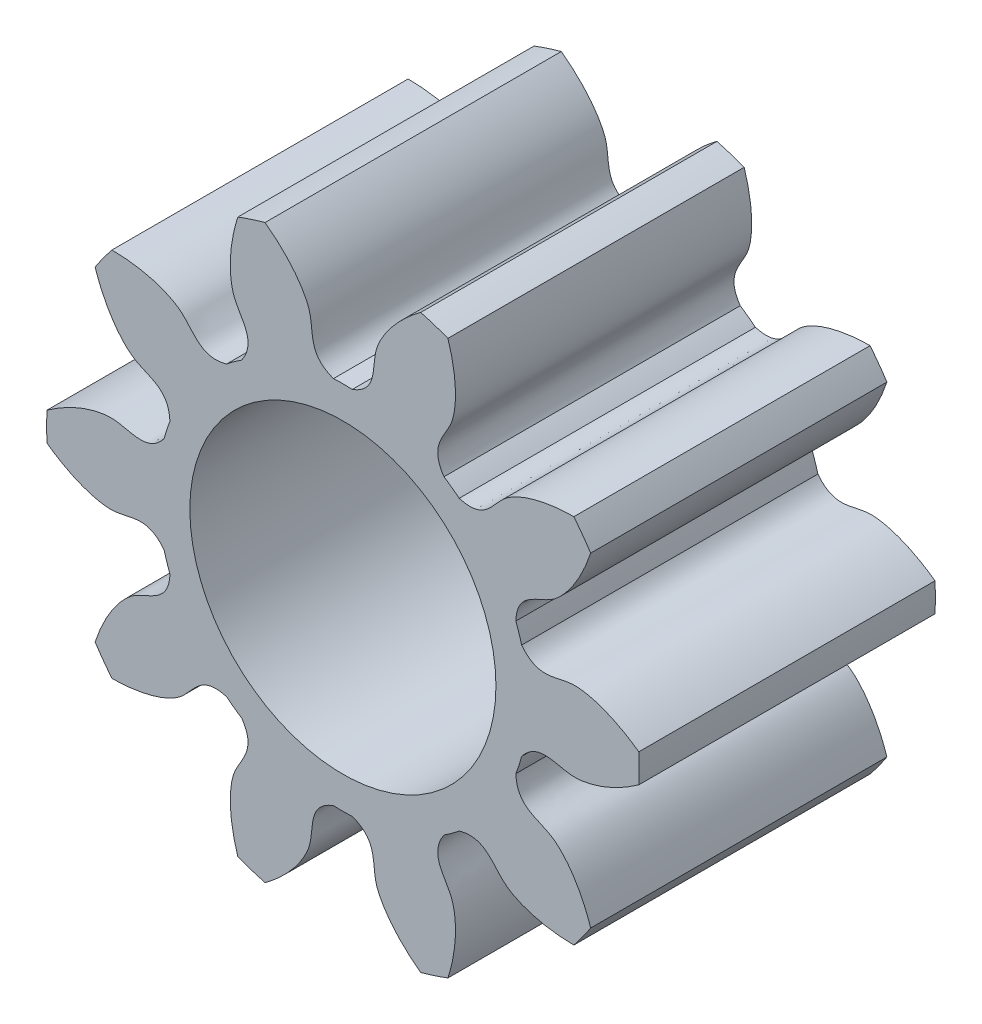
SolidWorks part; units mm, degrees
ref_plane "前视基准面" through (0, 0, 0) normal (0, 0, 1) x (1, 0, 0)
ref_plane "上视基准面" through (0, 0, 0) normal (0, 1, 0) x (1, 0, 0)
ref_plane "右视基准面" through (0, 0, 0) normal (1, 0, 0) x (0, 0, -1)
sketch "草图1" plane through (0, 0, 0) normal (0, 0, 1) x (1, 0, 0)
  circle A0 centre (0, 0) radius 3
extrude "凸台-拉伸1" add sketch "草图1" along normal blind 3
ref_axis "基准轴1" through (0, 0, -0.3) along (0, 0, 1)
sketch "草图2" plane through (0, 0, 0) normal (0, 0, 1) x (1, 0, 0)
  line L0 (0, 0) -> (0, 3) construction
  circle A0 centre (0, 0) radius 3 construction
  arc A1 (0.0952, 1.8726) -> (-0.0952, 1.8726) centre (0, 0) ccw
  arc A2 (2.1268, 3.3471) -> (-2.1268, 3.3471) centre (0, 0) ccw
  spline S0 degree 3 poles (0.0952, 1.8726) (0.3627, 1.9703) (0.2869, 2.1853) (0.3443, 2.3623) (0.3473, 2.3708) (0.3507, 2.38) (0.3546, 2.3901) (0.3591, 2.4009) (0.3642, 2.4126) (0.3699, 2.4249) (0.3763, 2.438) (0.3834, 2.4518) (0.3911, 2.4663) (0.3997, 2.4815) (0.409, 2.4972) (0.4191, 2.5136) (0.4301, 2.5306) (0.4419, 2.5481) (0.4546, 2.5662) (0.4682, 2.5848) (0.4828, 2.6038) (0.4983, 2.6233) (0.5148, 2.6432) (0.5323, 2.6634) (0.5509, 2.684) (0.5705, 2.7049) (0.5911, 2.7261) (0.6129, 2.7476) (0.6358, 2.7692) (0.6598, 2.791) (0.6849, 2.8129) (0.7112, 2.835) (0.7386, 2.8571) (0.7672, 2.8792) (0.7971, 2.9013) (0.8281, 2.9234) (0.8603, 2.9453) (0.8938, 2.9671) (0.9285, 2.9888) (0.9644, 3.0102) (1.0015, 3.0314) (1.0399, 3.0522) (1.0796, 3.0728) (1.1204, 3.0929) (1.1626, 3.1126) (1.2059, 3.1319) (1.2506, 3.1506) (1.2964, 3.1688) (1.3435, 3.1864) (1.3918, 3.2034) (1.4414, 3.2197) (1.4921, 3.2353) (1.5441, 3.2501) (1.5972, 3.2642) (1.6516, 3.2773) (1.7071, 3.2896) (1.7638, 3.301) (1.8216, 3.3114) (1.8805, 3.3208) (1.9405, 3.3291) (2.0227, 3.3388) (2.0849, 3.3443) (2.1268, 3.3471) knots 0 0 0 0 0.201721 0.204697 0.208023 0.211699 0.215726 0.220102 0.224829 0.229906 0.235332 0.241109 0.247237 0.253714 0.260541 0.267719 0.275246 0.283124 0.291352 0.29993 0.308858 0.318136 0.327765 0.337743 0.348072 0.358751 0.36978 0.381158 0.392888 0.404967 0.417396 0.430176 0.443305 0.456785 0.470615 0.484795 0.499325 0.514205 0.529435 0.545016 0.560946 0.577227 0.593858 0.610839 0.62817 0.645851 0.663882 0.682264 0.700995 0.720077 0.739509 0.759291 0.779423 0.799905 0.820737 0.84192 0.863452 0.885335 0.907568 0.930151 0.953084 1 1 1 1
  spline S1 degree 3 poles (-0.0952, 1.8726) (-0.3627, 1.9703) (-0.2869, 2.1853) (-0.3443, 2.3623) (-0.3473, 2.3708) (-0.3507, 2.38) (-0.3546, 2.3901) (-0.3591, 2.4009) (-0.3642, 2.4126) (-0.3699, 2.4249) (-0.3763, 2.438) (-0.3834, 2.4518) (-0.3911, 2.4663) (-0.3997, 2.4815) (-0.409, 2.4972) (-0.4191, 2.5136) (-0.4301, 2.5306) (-0.4419, 2.5481) (-0.4546, 2.5662) (-0.4682, 2.5848) (-0.4828, 2.6038) (-0.4983, 2.6233) (-0.5148, 2.6432) (-0.5323, 2.6634) (-0.5509, 2.684) (-0.5705, 2.7049) (-0.5911, 2.7261) (-0.6129, 2.7476) (-0.6358, 2.7692) (-0.6598, 2.791) (-0.6849, 2.8129) (-0.7112, 2.835) (-0.7386, 2.8571) (-0.7672, 2.8792) (-0.7971, 2.9013) (-0.8281, 2.9234) (-0.8603, 2.9453) (-0.8938, 2.9671) (-0.9285, 2.9888) (-0.9644, 3.0102) (-1.0015, 3.0314) (-1.0399, 3.0522) (-1.0796, 3.0728) (-1.1204, 3.0929) (-1.1626, 3.1126) (-1.2059, 3.1319) (-1.2506, 3.1506) (-1.2964, 3.1688) (-1.3435, 3.1864) (-1.3918, 3.2034) (-1.4414, 3.2197) (-1.4921, 3.2353) (-1.5441, 3.2501) (-1.5972, 3.2642) (-1.6516, 3.2773) (-1.7071, 3.2896) (-1.7638, 3.301) (-1.8216, 3.3114) (-1.8805, 3.3208) (-1.9405, 3.3291) (-2.0227, 3.3388) (-2.0849, 3.3443) (-2.1268, 3.3471) knots 0 0 0 0 0.201721 0.204697 0.208023 0.211699 0.215726 0.220102 0.224829 0.229906 0.235332 0.241109 0.247237 0.253714 0.260541 0.267719 0.275246 0.283124 0.291352 0.29993 0.308858 0.318136 0.327765 0.337743 0.348072 0.358751 0.36978 0.381158 0.392888 0.404967 0.417396 0.430176 0.443305 0.456785 0.470615 0.484795 0.499325 0.514205 0.529435 0.545016 0.560946 0.577227 0.593858 0.610839 0.62817 0.645851 0.663882 0.682264 0.700995 0.720077 0.739509 0.759291 0.779423 0.799905 0.820737 0.84192 0.863452 0.885335 0.907568 0.930151 0.953084 1 1 1 1
extrude "切除-拉伸1" cut sketch "草图2" along normal through all
pattern_circular "阵列(圆周)1" count 10 every 36 about axis through (0, 0, -0.3) along (0, 0, 1) of "切除-拉伸1"
sketch "草图3" plane through (0, 0, 0) normal (0, 0, 1) x (1, 0, 0)
  circle A0 centre (0, 0) radius 2.5 construction
  dimension "Dn" = 5
sketch "草图4" plane through (0, 0, 0) normal (0, 0, -1) x (-1, 0, 0)
  circle A0 centre (0, 0) radius 1.55
  dimension "D1" = 3.1
extrude "切除-拉伸2" cut sketch "草图4" against normal up to next
